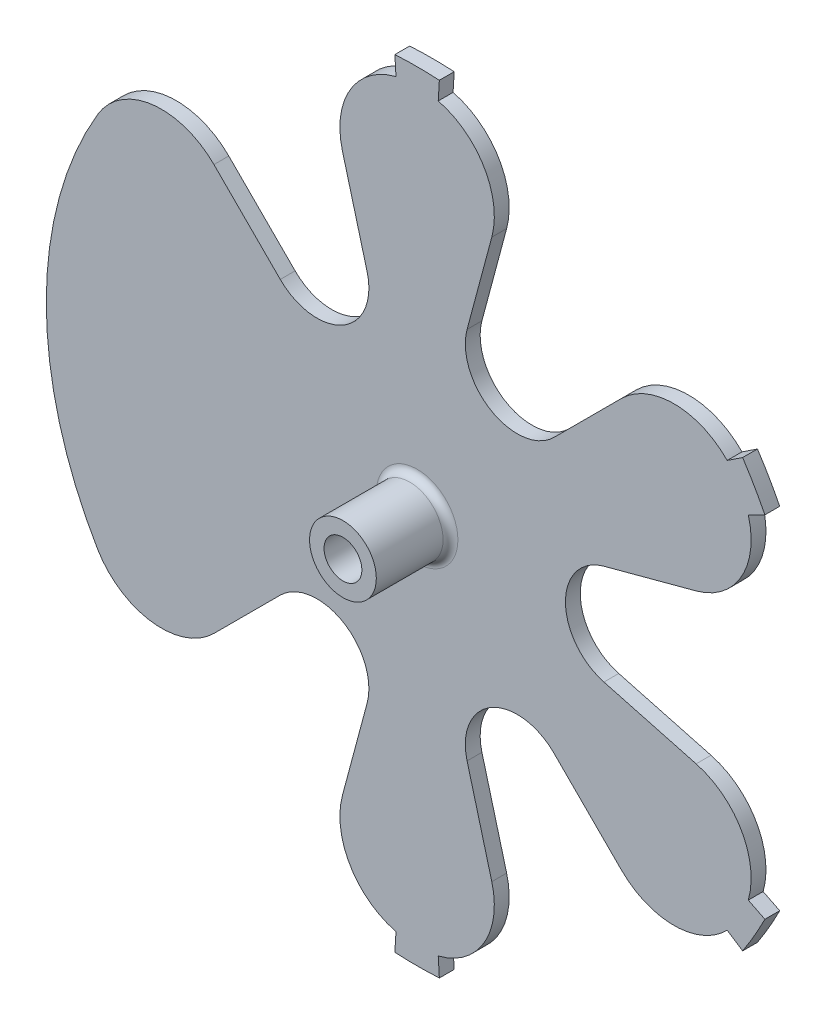
SolidWorks part; units mm, degrees
ref_plane "Front" through (0, 0, 0) normal (0, 0, 1) x (1, 0, 0)
ref_plane "Top" through (0, 0, 0) normal (0, 1, 0) x (1, 0, 0)
ref_plane "Right" through (0, 0, 0) normal (1, 0, 0) x (0, 0, -1)
sketch "Sketch1" plane through (0, 0, 0) normal (0, 0, 1) x (1, 0, 0)
  circle A0 centre (0, 0) radius 50
  dimension "D1" = 100
extrude "Boss-Extrude1" add sketch "Sketch1" along normal blind 2
sketch "Sketch3" plane through (0, 0, 0) normal (0, 1, 0) x (1, 0, 0)
  line L0 (0, 0) -> (0, -50) construction
  dimension "D1" = 50
sketch "Sketch5" plane through (0, 0, 2) normal (0, 0, 1) x (1, 0, 0)
  line L0 (0, 0) -> (0, 50) construction
  line L1 (-2.8474, 49.9189) -> (-3, 52.4142)
  line L2 (2.8474, 49.9189) -> (3, 52.4142)
  circle A0 centre (0, 0) radius 50 construction
  arc A1 (3, 52.4142) -> (-3, 52.4142) centre (0, 0) ccw
  arc A2 (-2.8474, 49.9189) -> (2.8474, 49.9189) centre (0, 0) cw
  point P13 (0, 52.5)
  dimension "D2" = 2.5
  dimension "D1" = 50
  dimension "D3" = 3.5
  dimension "D4" = 6
extrude "Boss-Extrude3" add sketch "Sketch5" against normal up to surface (2 mm away) up to face at (50, 0, 0)
sketch "Sketch4" plane through (0, 0, 2) normal (0, 0, 1) x (1, 0, 0)
  circle A0 centre (0, 0) radius 4.5
  circle A1 centre (0, 0) radius 2.55
  dimension "D1" = 9
  dimension "D2" = 5.1
extrude "Boss-Extrude2" add sketch "Sketch4" along normal blind 10
pattern_circular "CirPattern2" count 4 every 60 about axis through (0, 0, 0) along (0, 0, 1) of "Boss-Extrude3"
sketch "Sketch7" plane through (0, 0, 2) normal (0, 0, 1) x (1, 0, 0)
  line L0 (48.2932, 12.9524) -> (25.1883, 6.7615)
  line L1 (0, 0) -> (50, 0) construction
  line L2 (20, 0) -> (20, 45.8258) construction
  line L3 (48.2932, -12.9524) -> (25.1883, -6.7615)
  arc A0 (44.6547, -22.4935) -> (44.6547, 22.4935) centre (0, 0) ccw construction
  arc A1 (25.1883, 6.7615) -> (25.1883, -6.7615) centre (27, 0) ccw
  arc A2 (41.8073, 27.4253) -> (2.8474, 49.9189) centre (0, 0) ccw construction
  arc A3 (48.2932, 12.9524) -> (48.2932, -12.9524) centre (0, 0) cw
  dimension "D3" = 7
  dimension "D1" = 20
  dimension "D2" = 15
extrude "Cut-Extrude2" cut sketch "Sketch7" against normal up to next
pattern_circular "CirPattern3" count 3 every 60 about axis through (0, 0, 0) along (0, 0, 1) of "Cut-Extrude2"
fillet "Fillet1" radius 10 10 edges at (-35.3637, 35.3469, 1) (-12.9295, 48.2994, 1) (35.3637, -35.3469, 1) (12.9295, -48.2994, 1) (-12.9295, -48.2994, 1) (-35.3637, -35.3469, 1) (12.9295, 48.2994, 1) (35.3637, 35.3469, 1) (48.2932, 12.9524, 1) (48.2932, -12.9524, 1)
fillet "Fillet2" radius 1 2 edges at (2.55, 0, 2) (4.5, 0, 2)
